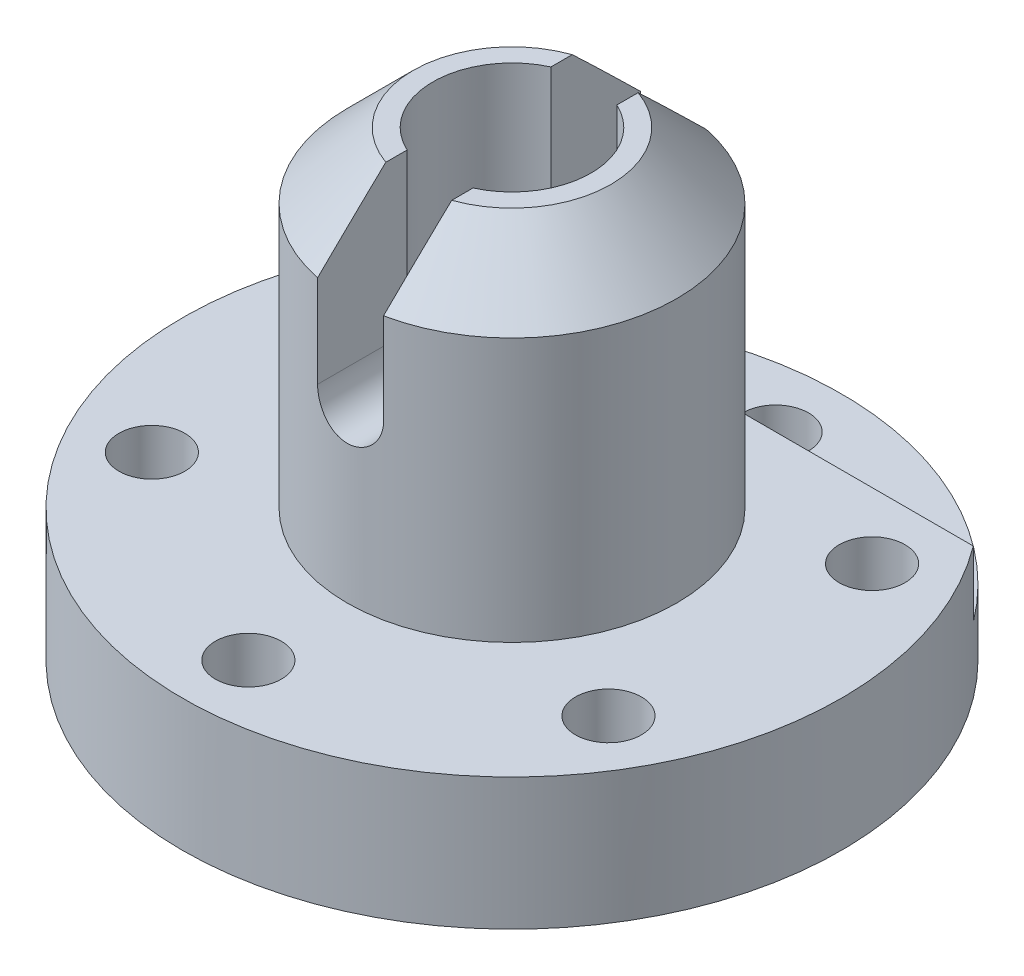
SolidWorks part; units mm, degrees
ref_plane "Front Plane" through (0, 0, 0) normal (0, 0, 1) x (1, 0, 0)
ref_plane "Top Plane" through (0, 0, 0) normal (0, 1, 0) x (1, 0, 0)
ref_plane "Right Plane" through (0, 0, 0) normal (1, 0, 0) x (0, 0, -1)
sketch "Sketch1" plane through (0, 0, 0) normal (0, 1, 0) x (1, 0, 0)
  line L0 (-20, 15) -> (20, 15)
  circle A0 centre (0, 0) radius 25
  circle A1 centre (0, 0) radius 12.5
  circle A2 centre (0, 0) radius 6
  dimension "D1" = 50
  dimension "D2" = 25
  dimension "D3" = 12
  dimension "D4" = 15
extrude "Boss-Extrude1" add sketch "Sketch1" along normal blind 10 contours A0
extrude "Boss-Extrude2" add sketch "Sketch1<3>" along normal blind 35 contours A1 A2 region at (-12.1464, 0, 0)
sketch "Sketch1<3>" plane through (0, 0, 0) normal (0, 1, 0) x (1, 0, 0) same geometry as "Sketch1"
extrude "Cut-Extrude1" cut sketch "Sketch1<5>" along normal up to surface (10 mm away) from offset 5 contours L0 A0 region at (0, 0, -19.0776) up to face at (0, 10, 12.5)
sketch "Sketch1<5>" plane through (0, 0, 0) normal (0, 1, 0) x (1, 0, 0) same geometry as "Sketch1"
sketch "Sketch2" plane through (0, 0, 0) normal (0, 0, 1) x (1, 0, 0)
  line L0 (0, 35) -> (0, 0) construction
  line L1 (12.5, 35) -> (-12.5, 35) construction
  line L3 (-2.5, 23) -> (2.5, 23)
  line L4 (-2.5, 23) -> (-2.5, 35)
  line L5 (-2.5, 35) -> (2.5, 35)
  line L6 (2.5, 23) -> (2.5, 35)
  circle A0 centre (0, 23) radius 2.5
  dimension "D1" = 5
  dimension "D2" = 12
extrude "Cut-Extrude2" cut sketch "Sketch2" against normal through all both and the other way through all contours L0 L5 L4 A0 | L5 L0 A0 L6 | A0 L0 L3 | L0 L3 A0 | L0 A0 L3 | L3 L0 A0 region at (1.287, 29.9662, 0) region at (-1.287, 29.9662, 0) region at (1.061, 24.061, 0) region at (-1.061, 24.061, 0) region at (1.061, 21.939, 0) region at (-1.061, 21.939, 0)
sketch "Sketch3" plane through (0, 0, 0) normal (0, 1, 0) x (1, 0, 0)
  line L0 (0, 0) -> (0, 28.2461) construction
  circle A0 centre (0, 20) radius 2.5
  dimension "D2" = 5
  dimension "D1" = 20
extrude "Cut-Extrude3" cut sketch "Sketch3" along normal through all contours A0
pattern_circular "CirPattern1" count 6 over 360 about axis through (0, 10, 0) along (0, 1, 0) of "Cut-Extrude3"
chamfer "Chamfer1" distance 5 angle 45 2 edges at (-12.5, 35, 0) (12.5, 35, 0)
